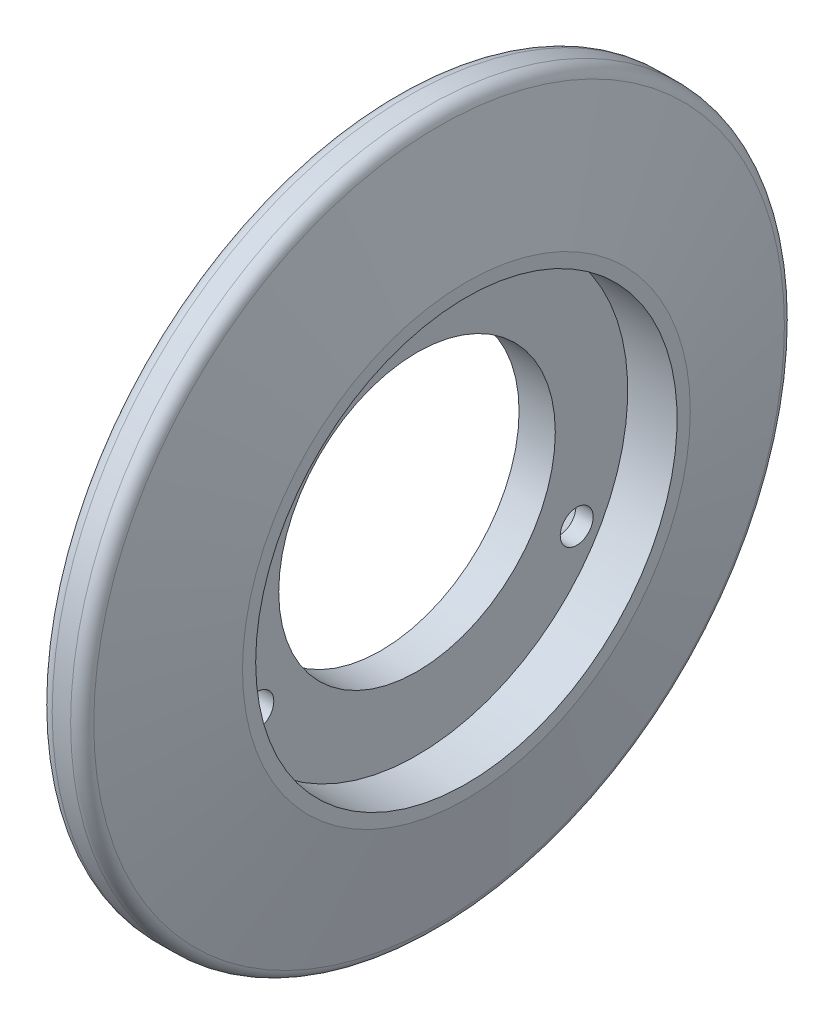
SolidWorks part; units mm, degrees
note: '?' marks a value the reader was unsure of.
ref_plane "Plan1" through (0, 0, 0) normal (0, 0, 1) x (1, 0, 0)
ref_plane "Plan2" through (0, 0, 0) normal (0, 1, 0) x (1, 0, 0)
ref_plane "Plan3" through (0, 0, 0) normal (1, 0, 0) x (0, 0, -1)
sketch "Esquisse1" plane through (0, 0, 0) normal (0, 0, 1) x (1, 0, 0)
  line L0 (-40, 0) -> (60, 0) construction
  line L1 (5.5, -34) -> (10, -54)
  line L2 (10, -54) -> (16, -54)
  line L3 (16, -54) -> (20.5, -34)
  line L4 (20.5, -34) -> (20.5, -32)
  line L5 (20.5, -32) -> (13, -32)
  line L6 (13, -32) -> (13, -21)
  line L7 (13, -21) -> (7.5, -21)
  line L8 (7.5, -21) -> (7.5, -33)
  line L9 (7.5, -33) -> (5.5, -33)
  line L10 (5.5, -33) -> (5.5, -34)
  dimension "D1" = 32
  dimension "D2" = 7.5
  dimension "D3" = 15
  dimension "D4" = 2
  dimension "D5" = 21
  dimension "D6" = 54
  dimension "D7" = 4.5
  dimension "D8" = 6
  dimension "D9" = 34
  dimension "D10" = 33
revolve "Base-Révolution" add sketch "Esquisse1" angle 360 about L0
fillet "Congé1" radius 2
hole_wizard "Perçage1" positions "Esquisse4" profile "Esquisse3" legacy
sketch "Esquisse4" plane through (7.5, 0, 0) normal (-1, 0, 0) x (0, 0, 1)
  point P0 (0, 28)
  dimension "D1" = 28
sketch "Esquisse3" plane through (7.5, 28, 0) normal (0, 1, 0) x (0, 0, 1)
  line L0 (0, 0) -> (0, 20)
  line L1 (0, 20) -> (2.5, 20)
  line L2 (2.5, 20) -> (2.5, 2.8759)
  line L3 (2.5, 2.8759) -> (5, 0)
  line L4 (5, 0) -> (0, 0)
  line L5 (0, -6.4453) -> (0, 115.525) construction
  line L6 (-2.5, 2.8759) -> (-5, 0) construction
  dimension "Diamètre" = 5
  dimension "Profondeur" = 20
  dimension "Angle fraisé" = 82
  dimension "Diamètre fraisé" = 10
ref_axis "Axe1" through (10, 0, 0) along (-1, 0, 0)?
pattern_circular "Répétition circulaire1" count 3 every 120 about axis through (10, 0, 0) along (-1, 0, 0)
